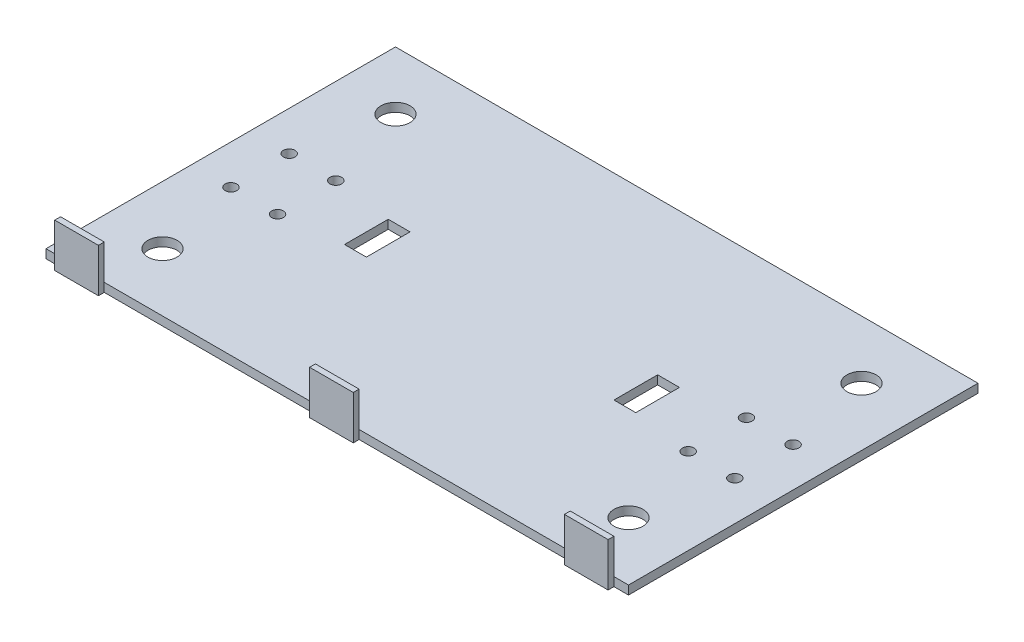
SolidWorks part; units mm, degrees
ref_plane "Front Plane" through (0, 0, 0) normal (0, 0, 1) x (1, 0, 0)
ref_plane "Top Plane" through (0, 0, 0) normal (0, 1, 0) x (1, 0, 0)
ref_plane "Right Plane" through (0, 0, 0) normal (1, 0, 0) x (0, 0, -1)
sketch "Sketch1" plane through (0, 0, 0) normal (0, 1, 0) x (1, 0, 0)
  line L1 (100, -60) -> (-100, -60)
  line L2 (100, -60) -> (100, 60)
  line L3 (100, 60) -> (-100, 60)
  line L4 (-100, -60) -> (-100, 60)
  line L5 (100, -60) -> (-100, 60) construction
  line L6 (100, 60) -> (-100, -60) construction
  point P0 (0, 0)
  dimension "D1" = 200
  dimension "D2" = 120
extrude "Boss-Extrude3" add sketch "Sketch1" along normal blind 1
sketch "Sketch3" plane through (0, 1, 0) normal (0, 1, 0) x (1, 0, 0)
  line L0 (-83.5355, 43.5355) -> (-76.4645, 36.4645) construction
  line L5 (-100, 60) -> (-100, -60) construction
  line L6 (-100, -60) -> (100, -60) construction
  line L7 (76.4645, 36.4645) -> (83.5355, 43.5355) construction
  line L11 (0, -55) -> (0, 55) construction
  line L15 (-55, 0) -> (55, 0) construction
  circle A0 centre (-80, 40) radius 5
  circle A2 centre (80, -40) radius 5
  circle A4 centre (80, 40) radius 5
  circle A5 centre (-80, -40) radius 5
  circle A7 centre (80, 40) radius 5
  circle A9 centre (80, -40) radius 5
  circle A11 centre (-80, -40) radius 5
  point P0 (0, 0)
  line M5 (-100, 60) -> (-100, -60)
  line M6 (-100, -60) -> (100, -60)
  line M7 (100, -60) -> (100, 60)
  line M8 (100, 60) -> (-100, 60)
  dimension "D3" = 10
  dimension "D4" = 10
  dimension "D5" = 10
  dimension "D6" = 10
  dimension "D1" = 20
  dimension "D2" = 20
extrude "Boss-Extrude4" add sketch "Sketch3" along normal blind 2 contours A0 M8 M5 | A5 M6 M5 | A4 M8 M7 | A2 M6 M7 region at (0, 1, 0)
sketch "Sketch8" plane through (0, 3, 0) normal (0, 1, 0) x (1, 0, 0)
  line L0 (0, -55) -> (0, 55) construction
  line L1 (-55, 0) -> (55, 0) construction
  circle A1 centre (-80, 40) radius 5
  circle A3 centre (80, 40) radius 5
  circle A5 centre (80, -40) radius 5
  circle A6 centre (-80, -40) radius 5
  dimension "D2" = 10
sketch "Sketch10" plane through (0, 0, 60) normal (0, 0, 1) x (1, 0, 0)
  line L0 (-100, 0) -> (100, 0) construction
  line L5 (-95, 0) -> (-80, 0)
  line L6 (-95, 0) -> (-95, 15)
  line L7 (-95, 15) -> (-80, 15)
  line L8 (-80, 0) -> (-80, 15)
  line L9 (-100, 3) -> (-100, 0) construction
  line L10 (0, -55) -> (0, 55) construction
  line L11 (95, 0) -> (80, 0)
  line L12 (95, 0) -> (95, 15)
  line L13 (95, 15) -> (80, 15)
  line L14 (80, 0) -> (80, 15)
  line L16 (-7.5, 0) -> (7.5, 0)
  line L17 (-7.5, 0) -> (-7.5, 15)
  line L18 (-7.5, 15) -> (7.5, 15)
  line L19 (7.5, 0) -> (7.5, 15)
  point P18 (0, 0)
  point P19 (0, 0)
  point P21 (0, 0)
  point P22 (-15.244, -1.9886)
  dimension "D1" = 15
  dimension "D2" = 15
  dimension "D3" = 5
  dimension "D4" = 15
  dimension "D5" = 15
extrude "Boss-Extrude6" add sketch "Sketch10" along normal blind 2
sketch "Sketch12" plane through (0, 0, 0) normal (0, -1, 0) x (1, 0, 0)
  line L0 (-100, -60) -> (-100, 60) construction
  line L1 (55, 0) -> (-55, 0) construction
  line L2 (0, -55) -> (0, 55) construction
  line L3 (50, -7.5) -> (42.5, -7.5)
  line L8 (-50, 7.5) -> (-42.5, 7.5)
  line L9 (-50, 7.5) -> (-50, -7.5)
  line L10 (-50, -7.5) -> (-42.5, -7.5)
  line L11 (-42.5, 7.5) -> (-42.5, -7.5)
  line L12 (42.5, 7.5) -> (42.5, -7.5)
  line L13 (50, 7.5) -> (42.5, 7.5)
  line L14 (50, 7.5) -> (50, -7.5)
  circle A0 centre (-86.5, 10) radius 2
  circle A1 centre (-70.5, 10) radius 2
  circle A2 centre (-70.5, -10) radius 2
  circle A3 centre (-86.5, -10) radius 2
  circle A4 centre (86.5, -10) radius 2
  circle A5 centre (70.5, -10) radius 2
  circle A6 centre (70.5, 10) radius 2
  circle A7 centre (86.5, 10) radius 2
  point P6 (-100, 0)
  point P28 (-50, 0)
  dimension "D1" = 13.5
  dimension "D3" = 16
  dimension "D2" = 10
  dimension "D4" = 15
  dimension "D5" = 7.5
  dimension "D6" = 50
extrude "Cut-Extrude1" cut sketch "Sketch12" against normal through all
extrude "Cut-Extrude2" cut sketch "Sketch8" against normal blind 10
